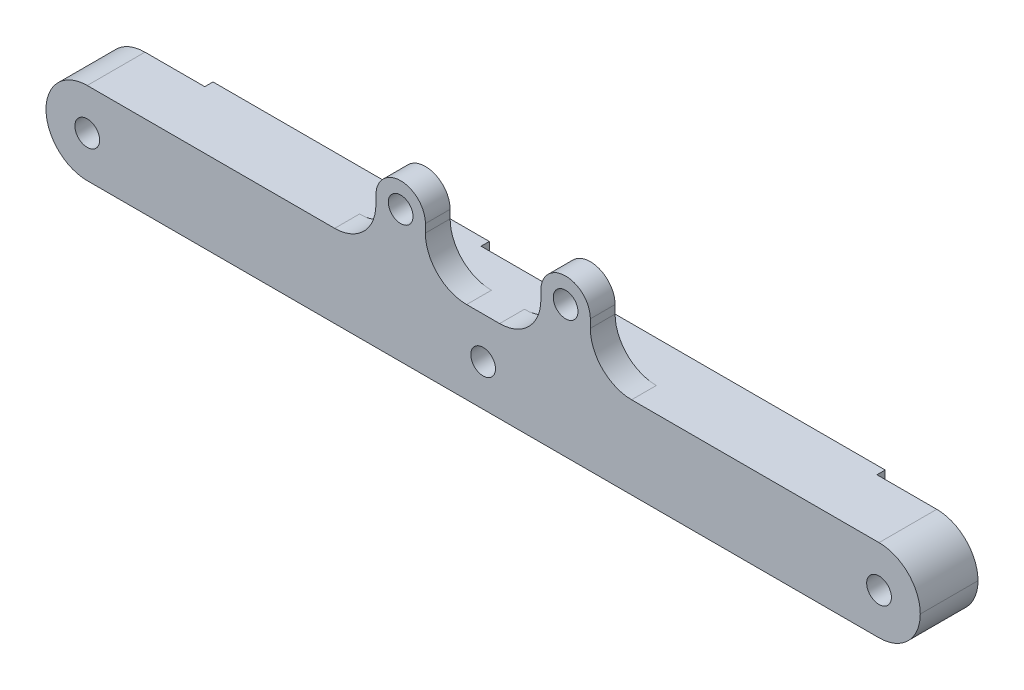
SolidWorks part; units mm, degrees
ref_plane "Front Plane" through (0, 0, 0) normal (0, 0, 1) x (1, 0, 0)
ref_plane "Top Plane" through (0, 0, 0) normal (0, 1, 0) x (1, 0, 0)
ref_plane "Right Plane" through (0, 0, 0) normal (1, 0, 0) x (0, 0, -1)
sketch "Sketch1" plane through (0, 0, 0) normal (0, 0, 1) x (1, 0, 0)
  line L1 (-53, -5) -> (53, -5)
  line L2 (-53, -5) -> (-53, 5)
  line L3 (-53, 5) -> (53, 5)
  line L4 (53, -5) -> (53, 5)
  line L5 (-53, -5) -> (53, 5) construction
  line L6 (-53, 5) -> (53, -5) construction
  point P0 (0, 0)
  dimension "D1" = 10
  dimension "D2" = 106
extrude "Boss-Extrude1" add sketch "Sketch1" along normal blind 7
fillet "Fillet1" radius 5 4 edges at (-53, -5, 3.5) (53, -5, 3.5) (53, 5, 3.5) (-53, 5, 3.5)
sketch "Sketch2" plane through (0, 0, 7) normal (0, 0, 1) x (1, 0, 0)
  circle A0 centre (-48, 0) radius 1.5
  circle A1 centre (48, 0) radius 1.5
  circle A2 centre (0, 0) radius 1.5
  dimension "D1" = 3
  dimension "D2" = 3
  dimension "D3" = 3
extrude "Cut-Extrude1" cut sketch "Sketch2" against normal through all
sketch "Sketch3" plane through (0, 0, 7) normal (0, 0, 1) x (1, 0, 0)
  line L0 (48, 5) -> (-48, 5) construction
  line L1 (7, 11) -> (7, 5)
  line L2 (7, 5) -> (13, 5)
  line L3 (13, 5) -> (13, 11)
  line L4 (-7, 11) -> (-7, 5)
  line L5 (-7, 5) -> (-13, 5)
  line L6 (-13, 5) -> (-13, 11)
  circle A0 centre (10, 11) radius 1.5
  circle A1 centre (-10, 11) radius 1.5
  arc A2 (13, 11) -> (7, 11) centre (10, 11) ccw
  arc A3 (-7, 11) -> (-13, 11) centre (-10, 11) ccw
  dimension "D1" = 6
  dimension "D2" = 3
  dimension "D3" = 3
  dimension "D4" = 6
  dimension "D5" = 10
  dimension "D6" = 20
  dimension "D7" = 6
  dimension "D8" = 6
extrude "Boss-Extrude2" add sketch "Sketch3" against normal blind 3
fillet "Fillet2" radius 5 1 edges at (-13, 5, 5.5)
fillet "Fillet3" radius 5 2 edges at (7, 5, 5.5) (-7, 5, 5.5)
fillet "Fillet4" radius 5 1 edges at (13, 5, 5.5)
sketch "Sketch4" plane through (0, 0, 0) normal (0, 0, -1) x (-1, 0, 0)
  line L0 (-48, 5) -> (48, 5) construction
  line L1 (-40.75, 5) -> (-7.25, 5)
  line L2 (-40.75, 5) -> (-40.75, -5)
  line L3 (-40.75, -5) -> (-7.25, -5)
  line L4 (-7.25, 5) -> (-7.25, -5)
  line L5 (48, -5) -> (-48, -5) construction
  line L7 (7.25, 5) -> (40.75, 5)
  line L8 (7.25, 5) -> (7.25, -5)
  line L9 (7.25, -5) -> (40.75, -5)
  line L10 (40.75, 5) -> (40.75, -5)
  circle A0 centre (0, 0) radius 1.5 construction
  circle A1 centre (48, 0) radius 1.5 construction
  circle A2 centre (-48, 0) radius 1.5 construction
  dimension "D1" = 7.25
  dimension "D2" = 14.5
  dimension "D3" = 7.25
  dimension "D4" = 7.25
extrude "Boss-Extrude3" add sketch "Sketch4" along normal blind 1
